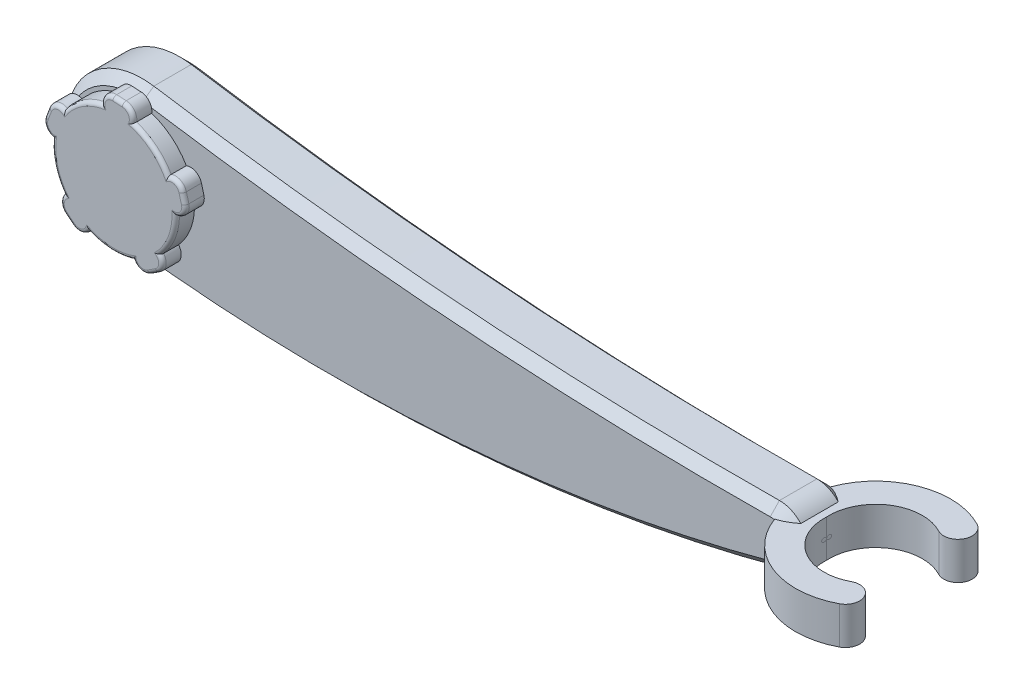
SolidWorks part; units mm, degrees
ref_plane "Ön Düzlem" through (0, 0, 0) normal (0, 0, 1) x (1, 0, 0)
ref_plane "Üst Düzlem" through (0, 0, 0) normal (0, 1, 0) x (1, 0, 0)
ref_plane "Sağ Düzlem" through (0, 0, 0) normal (1, 0, 0) x (0, 0, -1)
sketch "Çizim1" plane through (0, 0, 0) normal (0, 0, 1) x (1, 0, 0)
  line L0 (85, 0) -> (-85, 0) construction
  circle A0 centre (-85, 0) radius 20
  circle A1 centre (85, 0) radius 7.5
  arc A2 (-81.8718, 19.7538) -> (84.9221, 7.4996) centre (74.5404, 1007.4457) ccw
  arc A3 (-87.4615, -19.8479) -> (86.9844, -7.2327) centre (-32.0772, 426.7308) ccw
  point P4 (0, 0)
  dimension "D2" = 40
  dimension "D3" = 15
  dimension "D4" = 450
  dimension "D5" = 1000
  dimension "D1" = 170
extrude "Yükseklik-Ekstrüzyon1" add sketch "Çizim1" along normal mid plane 15 contours A0 | L0 A1 A2 A0 | A1 L0 A0 A3 | A1 region at (-3.1113, -10.4688, 0) region at (-6.4445, 6.0296, 0) region at (79.82, 5.1265, 0) region at (-72.1313, -14.5633, 0)
chamfer "Pah1" distance 2.5 angle 45 8 edges at (0.3802, -22.0971, -7.5) (-104.8037, 2.7953, -7.5) (92.4276, 1.0397, -7.5) (1.2686, 10.1337, -7.5) (0.3802, -22.0971, 7.5) (-104.8037, 2.7953, 7.5) (92.4276, 1.0397, 7.5) (1.2686, 10.1337, 7.5)
sketch "Çizim2" plane through (0, 0, 7.5) normal (0, 0, 1) x (1, 0, 0)
  circle A1 centre (-85, 0) radius 16.5
  dimension "D1" = 33
extrude "Yükseklik-Ekstrüzyon2" add sketch "Çizim2" along normal blind 5
sketch "Çizim3" plane through (0, 0, 12.5) normal (0, 0, 1) x (1, 0, 0)
  line L0 (-85, 0) -> (-68.9097, 0)
  line L2 (-66.0119, 3.7765) -> (-66.6676, 6.2235)
  line L3 (-71.0654, 8.0452) -> (-85, 0)
  line L4 (-85, 0) -> (-66.3397, 5) construction
  line L5 (-85, 0) -> (-80.0278, -15.3028)
  line L6 (-73.0426, -10.7665) -> (-85, 0)
  line L7 (-75.5407, -16.8918) -> (-73.416, -15.512)
  line L8 (-85, 0) -> (-98.0173, -9.4577)
  line L9 (-91.5445, -14.6992) -> (-85, 0)
  line L10 (-98.142, -14.2161) -> (-96.1731, -15.8105)
  line L11 (-85, 0) -> (-98.0173, 9.4577)
  line L12 (-101.0022, 1.6819) -> (-85, 0)
  line L13 (-102.5814, 8.1057) -> (-103.4893, 5.7406)
  line L14 (-85, 0) -> (-80.0278, 15.3028)
  line L15 (-88.3454, 15.7387) -> (-85, 0)
  line L16 (-82.724, 19.2257) -> (-85.2539, 19.3583)
  arc A0 (-73.0426, -10.7665) -> (-73.416, -15.512) centre (-75.05, -12.996) cw
  arc A1 (-66.0119, 3.7765) -> (-68.9097, 0) centre (-68.9097, 3) cw
  arc A2 (-71.0654, 8.0452) -> (-66.6676, 6.2235) centre (-69.5654, 5.4471) cw
  arc A3 (-75.5407, -16.8918) -> (-80.0278, -15.3028) centre (-77.1746, -14.3758) cw
  arc A4 (-91.5445, -14.6992) -> (-96.1731, -15.8105) centre (-94.2852, -13.479) cw
  arc A5 (-98.142, -14.2161) -> (-98.0173, -9.4577) centre (-96.254, -11.8847) cw
  arc A6 (-101.0022, 1.6819) -> (-103.4893, 5.7406) centre (-100.6886, 4.6655) cw
  arc A7 (-102.5814, 8.1057) -> (-98.0173, 9.4577) centre (-99.7807, 7.0306) cw
  arc A8 (-88.3454, 15.7387) -> (-85.2539, 19.3583) centre (-85.4109, 16.3624) cw
  arc A9 (-82.724, 19.2257) -> (-80.0278, 15.3028) centre (-82.881, 16.2299) cw
  circle A10 centre (-85, 0) radius 2
  point P11 (-67.6795, 10)
  circle M29 centre (-85, 0) radius 16.5
  dimension "D3" = 3
  dimension "D5" = 4
  dimension "D1" = 30
  dimension "D2" = 20
  dimension "D4" = 5
extrude "Yükseklik-Ekstrüzyon3" add sketch "Çizim3" against normal blind 5 contours A9 L16 A8 M29 | L4 L2 A2 M29 | L4 A1 L2 M29 | A3 L7 A0 M29 | A5 L10 A4 M29 | A7 L13 A6 M29 | A10 L11 A7 A6 L12 M29 | A10 L14 A9 A8 L15 M29 | A10 L4 A2 L3 M29 | L4 A10 L0 A1 M29 | A10 L5 A3 A0 L6 M29 | A10 L8 A5 A4 L9 M29 region at (-73.9833, 1.4506, 12.5) region at (-74.734, 4.2521, 12.5) region at (-78.9998, -9.2394, 12.5) region at (-91.9331, -8.5616, 12.5) region at (-95.285, 3.9481, 12.5) region at (-84.4234, 11.0017, 12.5) region at (-68.4431, 6.4563, 12.5) region at (-67.4332, 2.6871, 12.5) region at (-75.3796, -14.8141, 12.5) region at (-96.1162, -13.7273, 12.5) region at (-101.4905, 6.3301, 12.5) region at (-84.0756, 17.6395, 12.5)
fillet "Radyus1" radius 1 20 edges at (-103.3478, 3.2767, 12.5) (-103.0354, 6.9231, 12.5) (-100.8276, 9.842, 12.5) (-93.9865, 13.8381, 12.5) (-87.5535, 18.4623, 12.5) (-83.9889, 19.292, 12.5) (-80.5307, 18.0943, 12.5) (-74.6162, 12.8229, 12.5) (-68.2303, 8.1337, 12.5) (-66.3397, 5, 12.5) (-66.4102, 1.3409, 12.5) (-69.5959, -5.9131, 12.5) (-72.0823, -13.4355, 12.5) (-74.4784, -16.2019, 12.5) (-77.9802, -17.2656, 12.5) (-85.8635, -16.4774, 12.5) (-93.7861, -16.4372, 12.5) (-97.1575, -15.0133, 12.5) (-99.2513, -12.0116, 12.5) (-100.9378, -4.2705, 12.5)
sketch "Çizim5" plane through (0, 0, -7.5) normal (0, 0, -1) x (-1, 0, 0)
  circle A0 centre (85, 0) radius 5
  dimension "D1" = 10
extrude "Yükseklik-Ekstrüzyon4" add sketch "Çizim5" along normal blind 10
sketch "Çizim6" plane through (0, 0, 0) normal (0, 1, 0) x (1, 0, 0)
  line L0 (1.5252, 0) -> (92.5, 0) construction
  line L1 (92.5, -5) -> (92.5, 5) construction
  line L2 (84.9221, -5) -> (84.9221, 5) construction
  arc A0 (84.9221, 0) -> (114.2718, 18.3453) centre (104.9109, 0.6712) cw
  arc A1 (92.5, 0) -> (110.7282, 11.6547) centre (104.9109, 0.6712) cw
  arc A2 (114.2718, 18.3453) -> (110.7282, 11.6547) centre (112.5, 15) cw
  arc A3 (114.2718, -18.3453) -> (110.7282, -11.6547) centre (112.5, -15) ccw
  arc A4 (92.5, 0) -> (110.7282, -11.6547) centre (104.9109, -0.6712) ccw
  arc A5 (84.9221, 0) -> (114.2718, -18.3453) centre (104.9109, -0.6712) ccw
  point P14 (93.181, 0.2062)
  dimension "D1" = 20
  dimension "D2" = 15
  dimension "D3" = 20
extrude "Yükseklik-Ekstrüzyon5" add sketch "Çizim6" along normal mid plane 10
